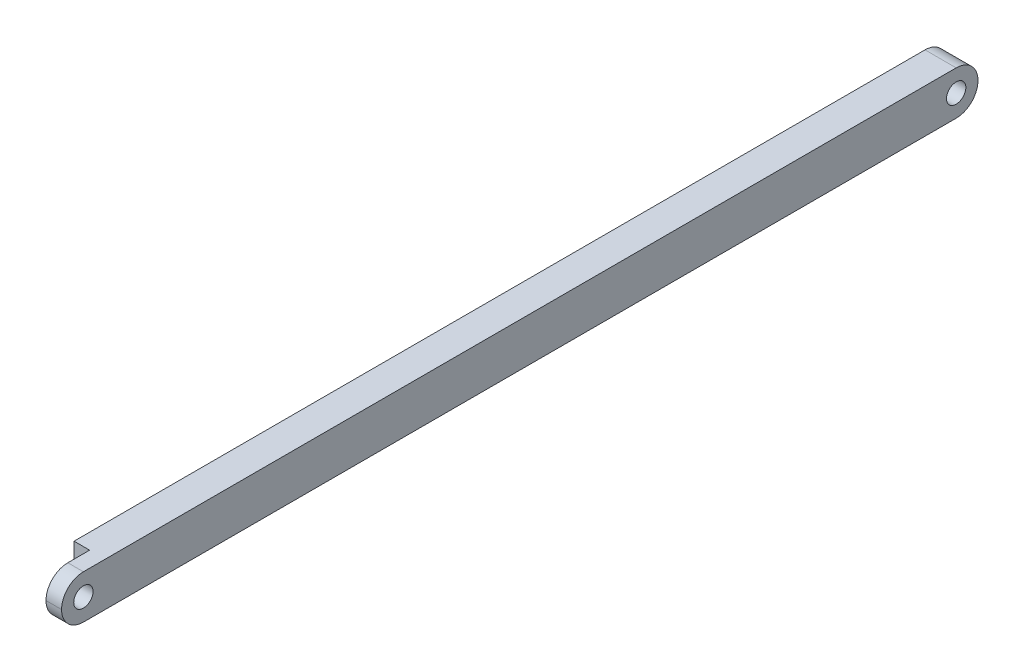
SolidWorks part; units mm, degrees
ref_plane "前视基准面" through (0, 0, 0) normal (0, 0, 1) x (1, 0, 0)
ref_plane "上视基准面" through (0, 0, 0) normal (0, 1, 0) x (1, 0, 0)
ref_plane "右视基准面" through (0, 0, 0) normal (1, 0, 0) x (0, 0, -1)
sketch "草图1" plane through (0, 0, 0) normal (0, 0, 1) x (1, 0, 0)
  line L1 (-2.5, 3.5) -> (2.5, 3.5)
  line L2 (-2.5, 3.5) -> (-2.5, -3.5)
  line L3 (-2.5, -3.5) -> (2.5, -3.5)
  line L4 (2.5, 3.5) -> (2.5, -3.5)
  line L5 (-2.5, 3.5) -> (2.5, -3.5) construction
  line L6 (-2.5, -3.5) -> (2.5, 3.5) construction
  point P0 (0, 0)
  dimension "D1" = 5
  dimension "D2" = 7
extrude "凸台-拉伸2" add sketch "草图1" along normal blind 140
fillet "圆角1" radius 3.5 2 edges at (0, -3.5, 0) (0, 3.5, 0)
sketch "草图3" plane through (2.5, 0, 0) normal (1, 0, 0) x (0, 0, -1)
  circle A0 centre (-3.5, 0) radius 1.55
  dimension "D1" = 3.1
extrude "切除-拉伸1" cut sketch "草图3" against normal through all
sketch "草图4" plane through (0, 0, 140) normal (0, 0, 1) x (1, 0, 0)
  line L0 (2.5, 3.5) -> (0, 3.5)
  line L1 (2.5, 3.5) -> (-2.5, 3.5) construction
  line L2 (0, 3.5) -> (0, -3.5)
  line L5 (0, -3.5) -> (2.5, -3.5)
  line L6 (2.5, -3.5) -> (2.5, 3.5)
  dimension "D1" = 2.5
extrude "凸台-拉伸3" add sketch "草图4" along normal blind 7
fillet "圆角2" radius 3.5 2 edges at (1.25, -3.5, 147) (1.25, 3.5, 147)
sketch "草图5" plane through (0, 0, 0) normal (-1, 0, 0) x (0, 0, 1)
  circle A0 centre (143.5, 0) radius 1.55
  dimension "D1" = 3.1
extrude "切除-拉伸2" cut sketch "草图5" against normal through all
